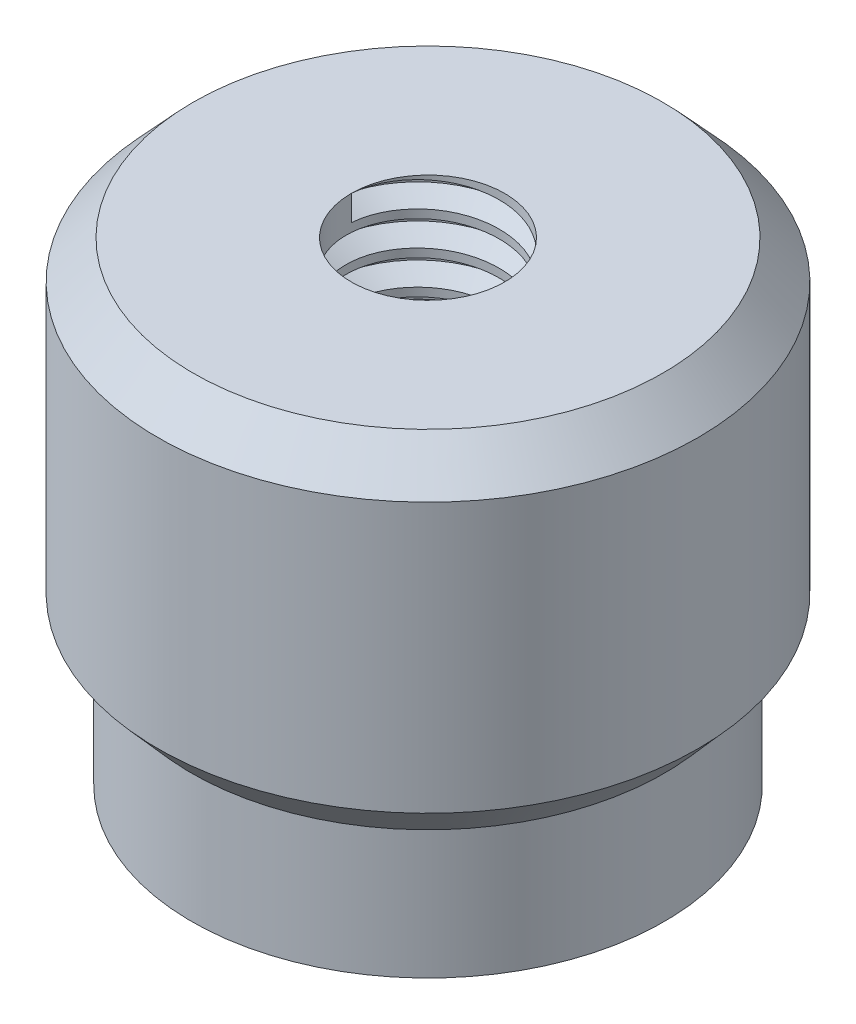
SolidWorks part; units mm, degrees
material "Nickel"
ref_plane "Front Plane" through (0, 0, 0) normal (0, 0, 1) x (1, 0, 0)
ref_plane "Top Plane" through (0, 0, 0) normal (0, 1, 0) x (1, 0, 0)
ref_plane "Right Plane" through (0, 0, 0) normal (1, 0, 0) x (0, 0, -1)
sketch "Sketch1" plane through (17.3702, -3.9554, 0) normal (0, 0, 1) x (1, 0, 0)
  line L8 (6.3686, 19.8798) -> (6.3686, -12.4854) construction
  line L13 (0.8266, 3.953) -> (0.8266, 6.9634)
  line L14 (0.8266, 6.9634) -> (0.0377, 7.8561)
  line L15 (0.0377, 7.8561) -> (0.0377, 14.1731)
  line L16 (0.0377, 14.1731) -> (0.8642, 15.0673)
  line L17 (0.8642, 15.0673) -> (4.5693, 15.0673)
  line L18 (4.5693, 15.0673) -> (4.5693, 3.953)
  line L19 (4.5693, 3.953) -> (0.8266, 3.953)
  point P0 (0.7364, 4.2687)
  dimension "D1" = 11.1143
revolve "Revolve3" add sketch "Sketch1" angle 360 about L8
thread "Thread2" pitch 0.7937 method cut profile "Thread Profile2" start angle 0, offset 0, length 10.668, pitch 0.7937, diameter 3.5986
ref_plane "Plane2" through (21.9395, 11.112, 0) normal (0, 0, 1) x (-1, 0, 0)
sketch "Thread Profile2" plane through (21.9395, 11.112, 0) normal (0, 0, 1) x (-1, 0, 0)
  line L0 (0, 0) -> (0, 0.7937) construction
  line L1 (0, 0) -> (0.4296, 0.248)
  line L2 (0.4296, 0.248) -> (0.4296, 0.3473)
  line L3 (0.4296, 0.3473) -> (0, 0.5953)
  line L4 (0.4296, 0.2977) -> (0, 0.2977) construction
  line L11 (0, 0) -> (0, 0.5953)
  point P2 (0, 0)
  dimension "Pitch" = 0.7937
  dimension "Profile_Angle" = 60
  dimension "Profile_Land" = 0.0992
  dimension "Profile_Height" = 0.4296
